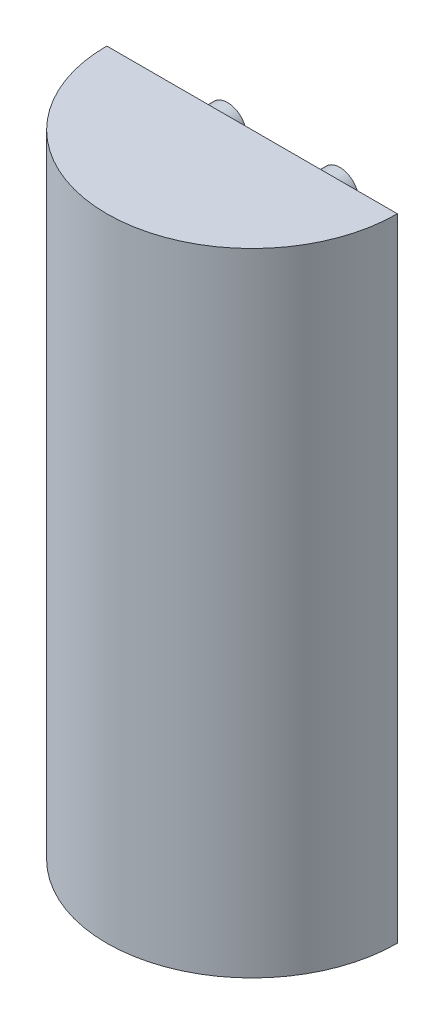
SolidWorks part; units mm, degrees
material "ABS"
ref_plane "Спереди" through (0, 0, 0) normal (0, 0, 1) x (1, 0, 0)
ref_plane "Сверху" through (0, 0, 0) normal (0, 1, 0) x (1, 0, 0)
ref_plane "Справа" through (0, 0, 0) normal (1, 0, 0) x (0, 0, -1)
sketch "Эскиз1" plane through (0, 0, 0) normal (0, 1, 0) x (1, 0, 0)
  line L0 (-23, 0) -> (23, 0)
  arc A0 (-23, 0) -> (23, 0) centre (0, 0) ccw
  dimension "D1" = 23
extrude "Бобышка-Вытянуть1" add sketch "Эскиз1" along normal blind 100
sketch "Эскиз2" plane through (0, 0, 0) normal (0, 0, -1) x (-1, 0, 0)
  line L0 (0, 100) -> (0, 0) construction
  line L1 (-23, 100) -> (23, 100) construction
  line L2 (-23, 50) -> (5.22, 50) construction
  line L3 (-23, 100) -> (-23, 0) construction
  line L4 (-8.89, 93.815) -> (8.89, 93.815) construction
  line L5 (-8.89, 93.815) -> (-8.89, 6.185) construction
  circle A0 centre (-8.89, 93.815) radius 3
  circle A1 centre (8.89, 93.815) radius 3
  circle A2 centre (-8.89, 6.185) radius 3
  circle A3 centre (8.89, 6.185) radius 3
  circle A4 centre (-8.89, 93.815) radius 0.9
  circle A5 centre (8.89, 93.815) radius 0.9
  circle A6 centre (8.89, 6.185) radius 0.9
  circle A7 centre (-8.89, 6.185) radius 0.9
  point P17 (0, 93.815)
  point P19 (-8.89, 50)
  dimension "D1" = 6
  dimension "D4" = 1.8
  dimension "D2" = 2
  dimension "D3" = 2
extrude "Бобышка-Вытянуть2" add sketch "Эскиз2" along normal blind 5
